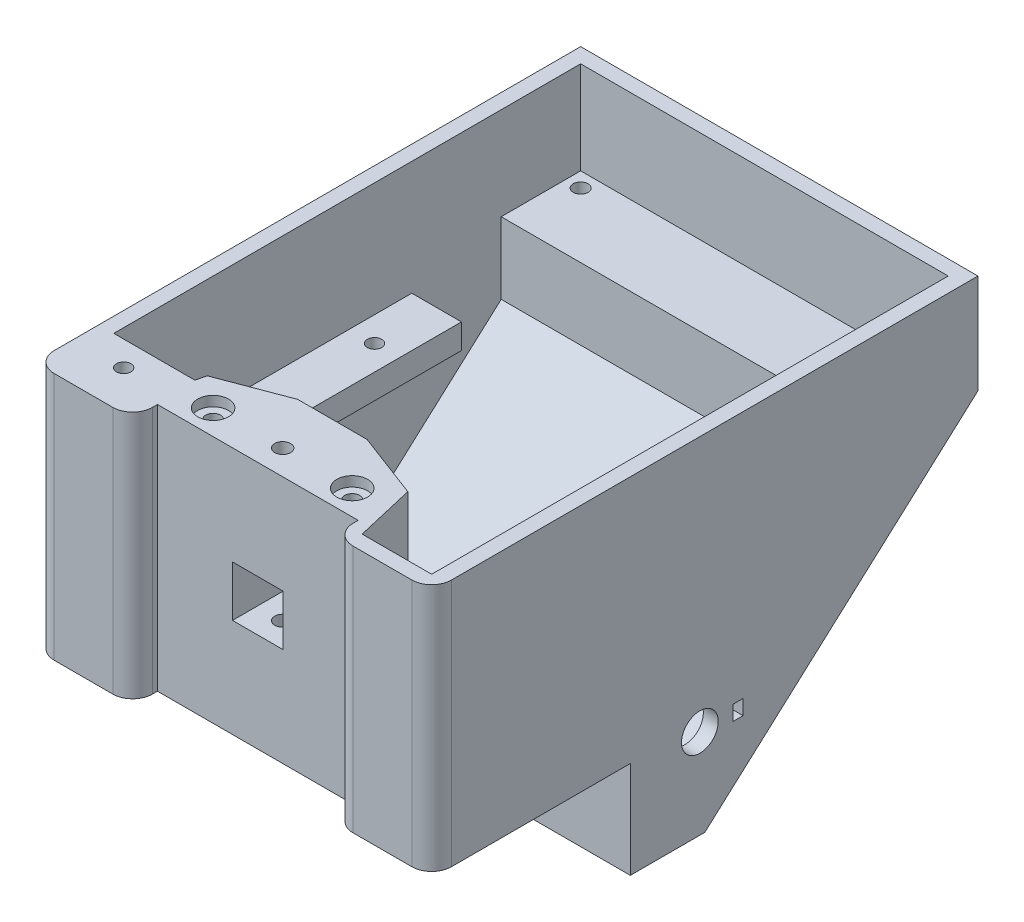
SolidWorks part; units mm, degrees
ref_plane "Спереди" through (0, 0, 0) normal (0, 0, 1) x (1, 0, 0)
ref_plane "Сверху" through (0, 0, 0) normal (0, 1, 0) x (1, 0, 0)
ref_plane "Справа" through (0, 0, 0) normal (1, 0, 0) x (0, 0, -1)
sketch "Sketch2" plane through (0, 0, 0) normal (1, 0, 0) x (0, 0, -1)
  line L0 (-27.3205, 20.9982) -> (-27.3205, -29.0018)
  line L1 (-27.3205, -29.0018) -> (12.6795, -29.0018)
  line L2 (12.6795, -29.0018) -> (12.6795, -48.5114)
  line L3 (12.6795, -48.5114) -> (27.6795, -48.5114)
  line L4 (82.6795, 20.9982) -> (82.6795, 0.9982)
  line L5 (82.6795, 20.9982) -> (-27.3205, 20.9982)
  line L6 (82.6795, 0.9982) -> (27.6795, -48.5114)
  dimension "D1" = 110
  dimension "D2" = 50
  dimension "D3" = 40
  dimension "D4" = 15
  dimension "D5" = 20
extrude "Boss-Extrude1" add sketch "Sketch2" along normal blind 80
shell "Shell1" thickness 3 removed face at (40, 20.9982, -27.6795)
sketch "Sketch3" plane through (0, 0, 24.3205) normal (0, 0, -1) x (-1, 0, 0)
  line L0 (-40, 20.9982) -> (-40, -26.0018) construction
  line L3 (-77, 20.9982) -> (-3, 20.9982) construction
  line L4 (-77, -26.0018) -> (-3, -26.0018) construction
  line L6 (-17, 20.9982) -> (-63, 20.9982)
  line L7 (-17, 20.9982) -> (-17, -26.0018)
  line L8 (-17, -26.0018) -> (-63, -26.0018)
  line L9 (-63, 20.9982) -> (-63, -26.0018)
  line L10 (-17, 20.9982) -> (-63, -26.0018) construction
  line L11 (-17, -26.0018) -> (-63, 20.9982) construction
  point P6 (-40, -2.5018)
  dimension "D1" = 46
extrude "Boss-Extrude2" add sketch "Sketch3" along normal blind 17
sketch "Sketch4" plane through (0, 0, 27.3205) normal (0, 0, 1) x (1, 0, 0)
  line L0 (0, 20.9982) -> (80, -29.0018) construction
  line L2 (45.1, -9.1018) -> (34.9, -9.1018)
  line L3 (45.1, -9.1018) -> (45.1, 1.0982)
  line L4 (45.1, 1.0982) -> (34.9, 1.0982)
  line L5 (34.9, -9.1018) -> (34.9, 1.0982)
  line L6 (45.1, -9.1018) -> (34.9, 1.0982) construction
  line L7 (45.1, 1.0982) -> (34.9, -9.1018) construction
  point P4 (40, -4.0018)
  dimension "D1" = 10.2
extrude "Cut-Extrude1" cut sketch "Sketch4" against normal up to surface (20 mm away) up to face at (40, -2.5018, 7.3205)
sketch "Sketch6" plane through (0, -29.0018, 0) normal (0, -1, 0) x (1, 0, 0)
  line L0 (40, 27.3205) -> (40, -12.6795) construction
  line L1 (47.5, -5.4795) -> (32.5, -5.4795)
  line L2 (47.5, -5.4795) -> (47.5, 7.3205)
  line L3 (47.5, 7.3205) -> (32.5, 7.3205)
  line L4 (32.5, -5.4795) -> (32.5, 7.3205)
  line L5 (47.5, -5.4795) -> (32.5, 7.3205) construction
  line L6 (47.5, 7.3205) -> (32.5, -5.4795) construction
  line L7 (80, -12.6795) -> (0, -12.6795) construction
  line L9 (80, 27.3205) -> (0, 27.3205) construction
  point P0 (40, 0.9205)
  dimension "D1" = 15
  dimension "D2" = 12.8
  dimension "D4" = 20
extrude "Cut-Extrude2" cut sketch "Sketch6" against normal up to surface (3 mm away) up to face at (40, -26.0018, 10.0705)
sketch "Sketch7" plane through (0, 0, 27.3205) normal (0, 0, 1) x (1, 0, 0)
  line L0 (40, 20.9982) -> (40, -29.0018) construction
  line L1 (80, 20.9982) -> (0, 20.9982) construction
  line L2 (80, -29.0018) -> (0, -29.0018) construction
  line L4 (60.2, -29.0018) -> (19.8, -29.0018)
  line L5 (60.2, -29.0018) -> (60.2, 20.9982)
  line L6 (60.2, 20.9982) -> (19.8, 20.9982)
  line L7 (19.8, -29.0018) -> (19.8, 20.9982)
  line L8 (60.2, -29.0018) -> (19.8, 20.9982) construction
  line L9 (60.2, 20.9982) -> (19.8, -29.0018) construction
  point P6 (40, -4.0018)
  dimension "D1" = 40.4
extrude "Cut-Extrude3" cut sketch "Sketch7" against normal blind 5
fillet "Fillet1" radius 4 4 edges at (19.8, -4.0018, 27.3205) (60.2, -4.0018, 27.3205) (80, -4.0018, 27.3205) (0, -4.0018, 27.3205)
sketch "Sketch12" plane through (0, 20.9982, 0) normal (0, 1, 0) x (1, 0, 0)
  line L0 (19.8, -22.3205) -> (19.8, -12.3205) construction
  line L1 (19.8, -12.3205) -> (60.2, -12.3205) construction
  line L2 (60.2, -12.3205) -> (60.2, -22.3205) construction
  line L3 (33, -7.3205) -> (19.8, -12.3205)
  line L4 (17, -7.3205) -> (63, -7.3205) construction
  line L5 (19.8, -12.3205) -> (17, -24.3205)
  line L6 (17, -24.3205) -> (17, -7.3205)
  line L7 (17, -7.3205) -> (33, -7.3205)
  line L8 (47, -7.3205) -> (63, -7.3205)
  line L9 (63, -7.3205) -> (63, -24.3205)
  line L10 (63, -24.3205) -> (60.2, -12.3205)
  line L11 (60.2, -12.3205) -> (47, -7.3205)
  dimension "D1" = 10
  dimension "D2" = 16
extrude "Cut-Extrude7" cut sketch "Sketch12" against normal up to surface (47 mm away) up to face at (40, -26.0018, 7.0205)
sketch "Sketch13" plane through (0, 20.9982, 0) normal (0, 1, 0) x (1, 0, 0)
  line L0 (19.8, -22.3205) -> (19.8, -12.3205) construction
  line L1 (19.8, -12.3205) -> (60.2, -12.3205) construction
  line L2 (60.2, -12.3205) -> (60.2, -22.3205) construction
  line L3 (60.2, -17.3205) -> (19.8, -17.3205) construction
  circle A0 centre (26, -17.3205) radius 1.5
  circle A1 centre (54, -17.3205) radius 1.5
  point P14 (40, -17.3205)
  dimension "D1" = 3
  dimension "D2" = 28
  dimension "D3" = 14
  dimension "D4" = 6.2
extrude "Cut-Extrude8" cut sketch "Sketch13" against normal blind 25
sketch "Sketch14" plane through (0, 20.9982, 0) normal (0, 1, 0) x (1, 0, 0)
  circle A0 centre (26, -17.3205) radius 3.1
  circle A1 centre (54, -17.3205) radius 3.1
  dimension "D1" = 6.2
extrude "Cut-Extrude9" cut sketch "Sketch14" against normal blind 2
sketch "Sketch17" plane through (77, 0, 0) normal (-1, 0, 0) x (0, 0, 1)
  line L0 (-45.6795, -2.0018) -> (-0.6795, -2.0018)
  line L1 (-0.6795, -2.0018) -> (-0.6795, -7.0018)
  line L2 (-0.6795, -7.0018) -> (-45.6795, -7.0018)
  line L3 (-45.6795, -7.0018) -> (-45.6795, -2.0018)
  line L4 (-79.6795, 20.9982) -> (24.3205, 20.9982) construction
  line L5 (-79.6795, 2.3342) -> (-79.6795, 20.9982) construction
  dimension "D1" = 45
  dimension "D2" = 5
  dimension "D3" = 23
  dimension "D4" = 34
extrude "Boss-Extrude5" add sketch "Sketch17" along normal up to surface (74 mm away) up to face at (3, -14.0994, -24.0865)
sketch "Sketch18" plane through (0, -2.0018, 0) normal (0, 1, 0) x (1, 0, 0)
  line L0 (40, 0.6795) -> (40, 45.6795) construction
  line L1 (3, 0.6795) -> (77, 0.6795) construction
  line L2 (3, 45.6795) -> (77, 45.6795) construction
  line L3 (77, 0.6795) -> (77, 45.6795) construction
  line L4 (13, 0.6795) -> (67, 0.6795)
  line L5 (13, 0.6795) -> (13, 45.6795)
  line L6 (13, 45.6795) -> (67, 45.6795)
  line L7 (67, 0.6795) -> (67, 45.6795)
  line L8 (13, 0.6795) -> (67, 45.6795) construction
  line L9 (13, 45.6795) -> (67, 0.6795) construction
  point P6 (40, 23.1795)
  dimension "D1" = 10
extrude "Cut-Extrude10" cut sketch "Sketch18" against normal up to next
sketch "Sketch19" plane through (0, -2.0018, 0) normal (0, 1, 0) x (1, 0, 0)
  line L0 (72, 45.6795) -> (72, 0.6795) construction
  line L1 (67, 45.6795) -> (77, 45.6795) construction
  line L2 (67, 0.6795) -> (77, 0.6795) construction
  line L3 (8, 45.6795) -> (8, 0.6795) construction
  line L4 (3, 45.6795) -> (13, 45.6795) construction
  line L5 (3, 0.6795) -> (13, 0.6795) construction
  circle A0 centre (72, 37.1795) radius 1.45
  circle A1 centre (72, 6.1795) radius 1.45
  circle A2 centre (8, 33.1795) radius 1.45
  circle A3 centre (8, 6.1795) radius 1.45
  point P20 (72, 23.1795)
  point P21 (8, 23.1795)
  dimension "D1" = 2.9
  dimension "D2" = 14
  dimension "D3" = 17
  dimension "D4" = 17
  dimension "D5" = 10
extrude "Cut-Extrude11" cut sketch "Sketch19" against normal up to next
sketch "Sketch21" plane through (0, -26.0018, 0) normal (0, 1, 0) x (1, 0, 0)
  line L0 (3, -24.3205) -> (3, -14.3205)
  line L1 (3, -24.3205) -> (3, 15.6795) construction
  line L2 (3, -14.3205) -> (19.3333, -14.3205)
  line L3 (19.8, -12.3205) -> (17, -24.3205) construction
  line L4 (19.3333, -14.3205) -> (17, -24.3205)
  line L6 (3, -24.3205) -> (17, -24.3205)
  dimension "D1" = 10
extrude "Boss-Extrude6" add sketch "Sketch21" along normal up to surface (47 mm away) up to face at (54, 20.9982, 20.4205)
sketch "Sketch22" plane through (0, 20.9982, 0) normal (0, 1, 0) x (1, 0, 0)
  line L0 (0, 82.6795) -> (0, -23.3205) construction
  line L1 (15.8, -27.3205) -> (4, -27.3205) construction
  circle A0 centre (10, -19.3205) radius 1.45
  dimension "D1" = 2.9
  dimension "D2" = 10
  dimension "D3" = 8
extrude "Cut-Extrude12" cut sketch "Sketch22" against normal through all
sketch "Sketch24" plane through (80, 0, 0) normal (1, 0, 0) x (0, 0, -1)
  line L0 (12.6795, -48.5114) -> (27.6795, -48.5114) construction
  line L1 (12.6795, -29.0018) -> (12.6795, -48.5114) construction
  line L2 (18.1795, -30.5114) -> (18.1795, -19.0114) construction
  line L3 (18.1795, -19.0114) -> (35.1795, -19.0114) construction
  line L4 (35.1795, -19.0114) -> (35.1795, -30.5114) construction
  line L5 (26.6795, -19.0114) -> (26.6795, -39.0114) construction
  line L6 (30.3795, -30.5114) -> (34.3795, -30.5114) construction
  line L8 (33.3795, -32.0114) -> (35.3795, -32.0114)
  line L9 (33.3795, -32.0114) -> (33.3795, -29.0114)
  line L10 (33.3795, -29.0114) -> (35.3795, -29.0114)
  line L11 (35.3795, -32.0114) -> (35.3795, -29.0114)
  line L12 (33.3795, -32.0114) -> (35.3795, -29.0114) construction
  line L13 (33.3795, -29.0114) -> (35.3795, -32.0114) construction
  circle A0 centre (26.6795, -30.5114) radius 3.7
  circle A1 centre (26.6795, -30.5114) radius 8.5 construction
  dimension "D1" = 7.4
  dimension "D2" = 17
  dimension "D3" = 18
  dimension "D4" = 14
  dimension "D5" = 20
  dimension "D6" = 4
  dimension "D7" = 2
  dimension "D8" = 3
extrude "Cut-Extrude13" cut sketch "Sketch24" against normal up to next
sketch "Sketch26" plane through (3, 0, 0) normal (1, 0, 0) x (0, 0, -1)
  line L0 (79.6795, 2.3342) -> (63.6795, 2.3342)
  line L1 (63.6795, 2.3342) -> (63.6795, -12.0686)
  line L2 (26.5281, -45.5114) -> (79.6795, 2.3342) construction
  line L3 (63.6795, -12.0686) -> (79.6795, 2.3342)
  dimension "D1" = 16
extrude "Boss-Extrude7" add sketch "Sketch26" along normal up to surface (74 mm away) up to face at (77, -30.5114, -34.3795)
sketch "Sketch27" plane through (0, 2.3342, 0) normal (0, 1, 0) x (1, 0, 0)
  line L0 (3, 76.6795) -> (77, 76.6795) construction
  line L1 (3, 79.6795) -> (3, 63.6795) construction
  line L2 (77, 79.6795) -> (77, 63.6795) construction
  line L3 (80, 82.6795) -> (0, 82.6795) construction
  circle A0 centre (6, 76.6795) radius 1.5
  circle A1 centre (74, 76.6795) radius 1.5
  point P10 (40, 76.6795)
  dimension "D1" = 3
  dimension "D2" = 68
  dimension "D3" = 34
  dimension "D4" = 6
extrude "Cut-Extrude14" cut sketch "Sketch27" against normal blind 10
sketch "Sketch28" plane through (0, 2.3342, 0) normal (0, 1, 0) x (1, 0, 0)
  line L1 (74, 79.9295) -> (71.1854, 78.3045)
  line L2 (71.1854, 78.3045) -> (71.1854, 75.0545)
  line L3 (71.1854, 75.0545) -> (74, 73.4295)
  line L4 (74, 73.4295) -> (76.8146, 75.0545)
  line L5 (76.8146, 75.0545) -> (76.8146, 78.3045)
  line L6 (76.8146, 78.3045) -> (74, 79.9295)
  line L7 (6, 73.4295) -> (8.8146, 75.0545)
  line L8 (8.8146, 75.0545) -> (8.8146, 78.3045)
  line L9 (8.8146, 78.3045) -> (6, 79.9295)
  line L10 (6, 79.9295) -> (3.1854, 78.3045)
  line L11 (3.1854, 78.3045) -> (3.1854, 75.0545)
  line L12 (3.1854, 75.0545) -> (6, 73.4295)
  circle A0 centre (74, 76.6795) radius 3.25 construction
  circle A1 centre (6, 76.6795) radius 3.25 construction
  dimension "D1" = 6.5
extrude "Cut-Extrude15" cut sketch "Sketch28" against normal blind 32 from offset 3 offset against normal yes
sketch "Sketch29" plane through (0, -29.0018, 0) normal (0, -1, 0) x (1, 0, 0)
  line L0 (0, 23.3205) -> (0, -12.6795) construction
  line L1 (7.1854, 17.6955) -> (10, 16.0705)
  line L2 (10, 16.0705) -> (12.8146, 17.6955)
  line L3 (12.8146, 17.6955) -> (12.8146, 20.9455)
  line L4 (12.8146, 20.9455) -> (10, 22.5705)
  line L5 (10, 22.5705) -> (7.1854, 20.9455)
  line L6 (7.1854, 20.9455) -> (7.1854, 17.6955)
  circle A0 centre (10, 19.3205) radius 3.25 construction
  dimension "D1" = 6.5
extrude "Cut-Extrude16" cut sketch "Sketch29" against normal blind 30
sketch "Sketch30" plane through (0, -26.0018, 0) normal (0, 1, 0) x (1, 0, 0)
  line L0 (77, -24.3205) -> (63, -24.3205)
  line L1 (63, -24.3205) -> (60.2, -12.3205)
  line L2 (63, -24.3205) -> (60.2, -12.3205) construction
  line L3 (60.2, -12.3205) -> (77, -12.3205)
  line L4 (77, -24.3205) -> (77, 15.6795) construction
  line L5 (77, -12.3205) -> (77, -24.3205)
  dimension "D1" = 12
extrude "Boss-Extrude8" add sketch "Sketch30" along normal blind 20
sketch "Sketch31" plane through (0, -6.0018, 0) normal (0, 1, 0) x (1, 0, 0)
  line L0 (76, -27.3205) -> (64.2, -27.3205) construction
  line L1 (80, -23.3205) -> (80, 12.6795) construction
  circle A0 centre (72, -21.3205) radius 1.5
  dimension "D3" = 3
  dimension "D1" = 6
  dimension "D2" = 8
extrude "Cut-Extrude17" cut sketch "Sketch31" against normal through all
sketch "Sketch32" plane through (0, -29.0018, 0) normal (0, -1, 0) x (1, 0, 0)
  line L1 (72, 24.5705) -> (69.1854, 22.9455)
  line L2 (69.1854, 22.9455) -> (69.1854, 19.6955)
  line L3 (69.1854, 19.6955) -> (72, 18.0705)
  line L4 (72, 18.0705) -> (74.8146, 19.6955)
  line L5 (74.8146, 19.6955) -> (74.8146, 22.9455)
  line L6 (74.8146, 22.9455) -> (72, 24.5705)
  circle A0 centre (72, 21.3205) radius 3.25 construction
  dimension "D1" = 6.5
extrude "Cut-Extrude18" cut sketch "Sketch32" against normal blind 15
sketch "Sketch33" plane through (0, -2.0018, 0) normal (0, 1, 0) x (1, 0, 0)
  line L0 (67, 40.6795) -> (77, 40.6795)
  line L1 (67, 0.6795) -> (67, 45.6795) construction
  line L2 (77, 0.6795) -> (77, 45.6795) construction
  line L3 (77, 40.6795) -> (77, 45.6795)
  line L4 (77, 45.6795) -> (67, 45.6795)
  line L5 (67, 45.6795) -> (67, 40.6795)
  dimension "D1" = 5
extrude "Cut-Extrude19" cut sketch "Sketch33" against normal up to next
sketch "Sketch34" plane through (0, 20.9982, 0) normal (0, 1, 0) x (1, 0, 0)
  line L0 (54, -17.3205) -> (26, -17.3205) construction
  circle A0 centre (40, -17.3205) radius 1.6
  dimension "D1" = 3.2
extrude "Cut-Extrude20" cut sketch "Sketch34" against normal through all
sketch "Sketch36" plane through (0, -29.0018, 0) normal (0, -1, 0) x (1, 0, 0)
  line L1 (38.375, 20.1351) -> (36.75, 17.3205)
  line L2 (36.75, 17.3205) -> (38.375, 14.5059)
  line L3 (38.375, 14.5059) -> (41.625, 14.5059)
  line L4 (41.625, 14.5059) -> (43.25, 17.3205)
  line L5 (43.25, 17.3205) -> (41.625, 20.1351)
  line L6 (41.625, 20.1351) -> (38.375, 20.1351)
  circle A0 centre (40, 17.3205) radius 3.25 construction
  dimension "D1" = 6.5
extrude "Cut-Extrude22" cut sketch "Sketch36" against normal blind 14
sketch "Sketch37" plane through (80, 0, 0) normal (1, 0, 0) x (0, 0, -1)
  line L0 (-23.3205, -16.5114) -> (63.2281, -16.5114) construction
  line L1 (-23.3205, 20.9982) -> (-23.3205, -29.0018) construction
  line L2 (27.6795, -48.5114) -> (82.6795, 0.9982) construction
  line L3 (30.3795, -30.5114) -> (22.9795, -30.5114) construction
  circle A0 centre (-3.3205, -16.5114) radius 3.2
  circle A1 centre (26.6795, -30.5114) radius 3.7 construction
  point P14 (26.6795, -30.5114)
  dimension "D1" = 6.4
  dimension "D2" = 14
  dimension "D3" = 20
sketch "Sketch40" plane through (3, 0, 0) normal (1, 0, 0) x (0, 0, -1)
  line L0 (18.1795, -30.5114) -> (18.1795, -19.0114) construction
  line L1 (18.1795, -19.0114) -> (35.1795, -19.0114) construction
  line L2 (35.1795, -19.0114) -> (35.1795, -30.5114) construction
  line L3 (26.6795, -19.0114) -> (26.6795, -39.0114) construction
  line L4 (30.3795, -30.5114) -> (34.3795, -30.5114) construction
  line L5 (33.3795, -32.0114) -> (35.3795, -32.0114) construction
  line L6 (33.3795, -32.0114) -> (33.3795, -29.0114) construction
  line L7 (33.3795, -29.0114) -> (35.3795, -29.0114) construction
  line L8 (35.3795, -32.0114) -> (35.3795, -29.0114) construction
  line L9 (33.3795, -32.0114) -> (35.3795, -29.0114) construction
  line L10 (33.3795, -29.0114) -> (35.3795, -32.0114) construction
  line L13 (22.9795, -30.5114) -> (18.9795, -30.5114) construction
  line L14 (12.6795, -29.0018) -> (12.6795, -48.5114) construction
  line L15 (17.9795, -29.0114) -> (19.9795, -29.0114)
  line L16 (17.9795, -29.0114) -> (17.9795, -32.0114)
  line L17 (17.9795, -32.0114) -> (19.9795, -32.0114)
  line L18 (19.9795, -29.0114) -> (19.9795, -32.0114)
  line L19 (17.9795, -29.0114) -> (19.9795, -32.0114) construction
  line L20 (17.9795, -32.0114) -> (19.9795, -29.0114) construction
  line L21 (12.6795, -48.5114) -> (27.6795, -48.5114) construction
  circle A0 centre (26.6795, -30.5114) radius 3.7
  circle A1 centre (26.6795, -30.5114) radius 8.5 construction
  dimension "D4" = 17
  dimension "D5" = 17
  dimension "D11" = 7.4
  dimension "D1" = 3
  dimension "D2" = 2
  dimension "D3" = 4
  dimension "D6" = 2
  dimension "D7" = 3
  dimension "D8" = 4
  dimension "D9" = 14
  dimension "D10" = 18
extrude "Cut-Extrude24" cut sketch "Sketch40" against normal up to next
